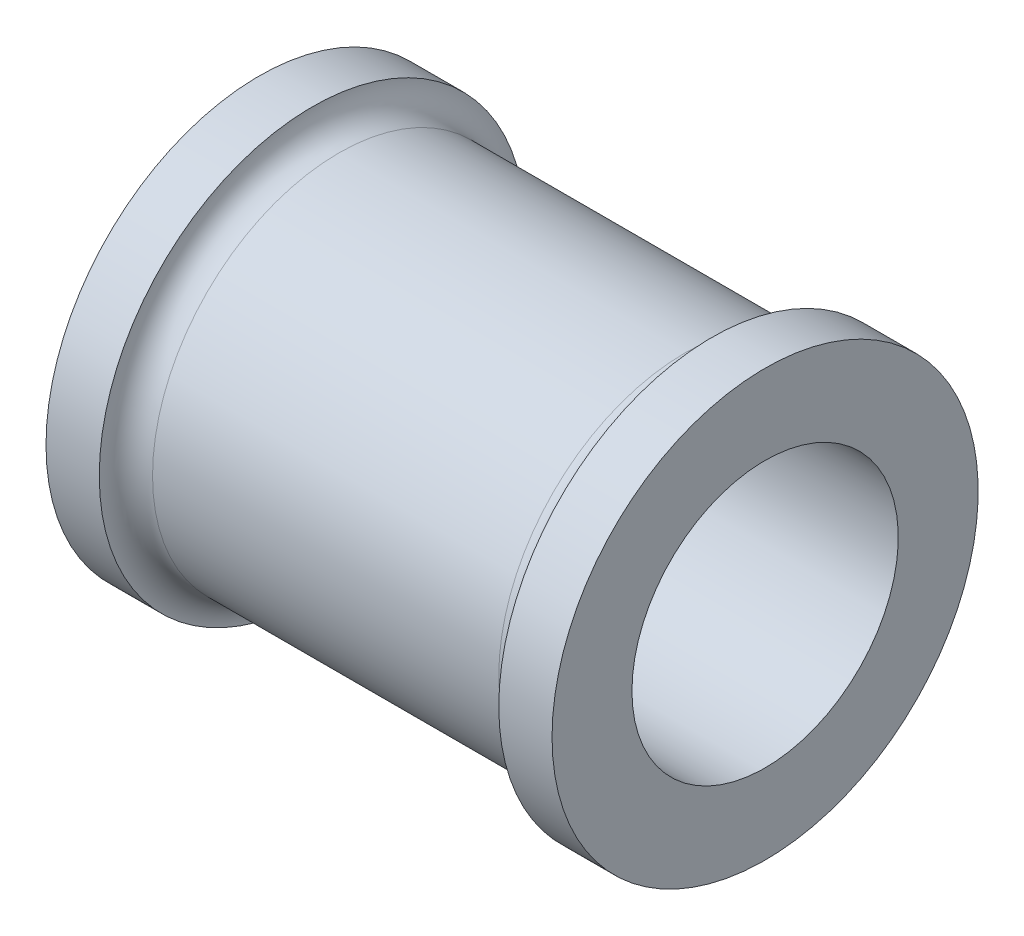
SolidWorks part; units mm, degrees
ref_plane "Front Plane" through (0, 0, 0) normal (0, 0, 1) x (1, 0, 0)
ref_plane "Top Plane" through (0, 0, 0) normal (0, 1, 0) x (1, 0, 0)
ref_plane "Right Plane" through (0, 0, 0) normal (1, 0, 0) x (0, 0, -1)
sketch "Sketch1" plane through (0, 0, 0) normal (0, 1, 0) x (1, 0, 0)
  line L9 (0, 7) -> (15, 7)
  line L11 (15, 8) -> (17, 8)
  line L12 (17, 8) -> (17, 5)
  line L13 (17, 5) -> (-2, 5)
  line L14 (-2, 5) -> (-2, 8)
  line L15 (-2, 8) -> (0, 8)
  line L16 (0, 0) -> (0, 2.8404) construction
  line L17 (0, 0) -> (6.1209, 0) construction
  line L18 (0, 8) -> (0, 7)
  line L19 (15, 8) -> (15, 7)
  dimension "D1" = 19
  dimension "D2" = 2
  dimension "D3" = 2
  dimension "D5" = 5
  dimension "D6" = 3
  dimension "D7" = 3
revolve "Revolve1" add sketch "Sketch1" angle 360 about L17
fillet "Fillet1" radius 1 2 edges at (0, 0, 7) (15, 0, 7)
